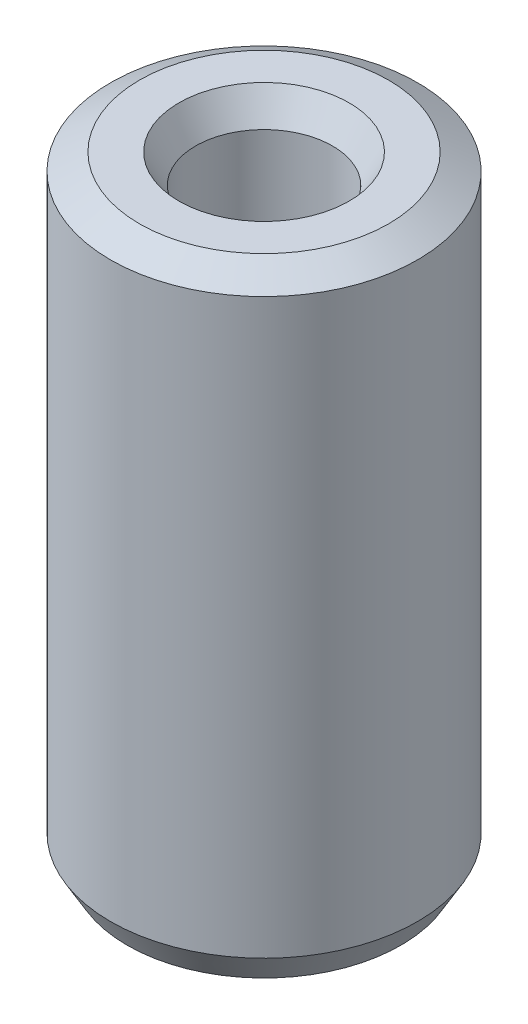
SolidWorks part; units mm, degrees
ref_plane "Front Plane" through (0, 0, 0) normal (0, 0, 1) x (1, 0, 0)
ref_plane "Top Plane" through (0, 0, 0) normal (0, 1, 0) x (1, 0, 0)
ref_plane "Right Plane" through (0, 0, 0) normal (1, 0, 0) x (0, 0, -1)
sketch "Sketch1" plane through (0, 0, 0) normal (0, 1, 0) x (1, 0, 0)
  circle A0 centre (0, 0) radius 22.5
  dimension "SLEEVE_OD" = 45
extrude "Boss-Extrude1" add sketch "Sketch1" along normal blind 90.6886
sketch "Sketch2" plane through (0, 0, 0) normal (0, 1, 0) x (1, 0, 0)
  circle A0 centre (0, 0) radius 10.0313
  dimension "BORE_D" = 20.0627
extrude "Cut-Extrude1" cut sketch "Sketch2" along normal through all
chamfer "Chamfer1" distance 2.4508 angle 60 4 edges at (0, 90.6886, 10.0313) (0, 0, 10.0313) (0, 0, 22.5) (0, 90.6886, 22.5) first distance on face at (0, 90.6886, 10.0313) first distance on face at (0, 0, 10.0313) first distance on face at (0, 90.6886, 22.5)
